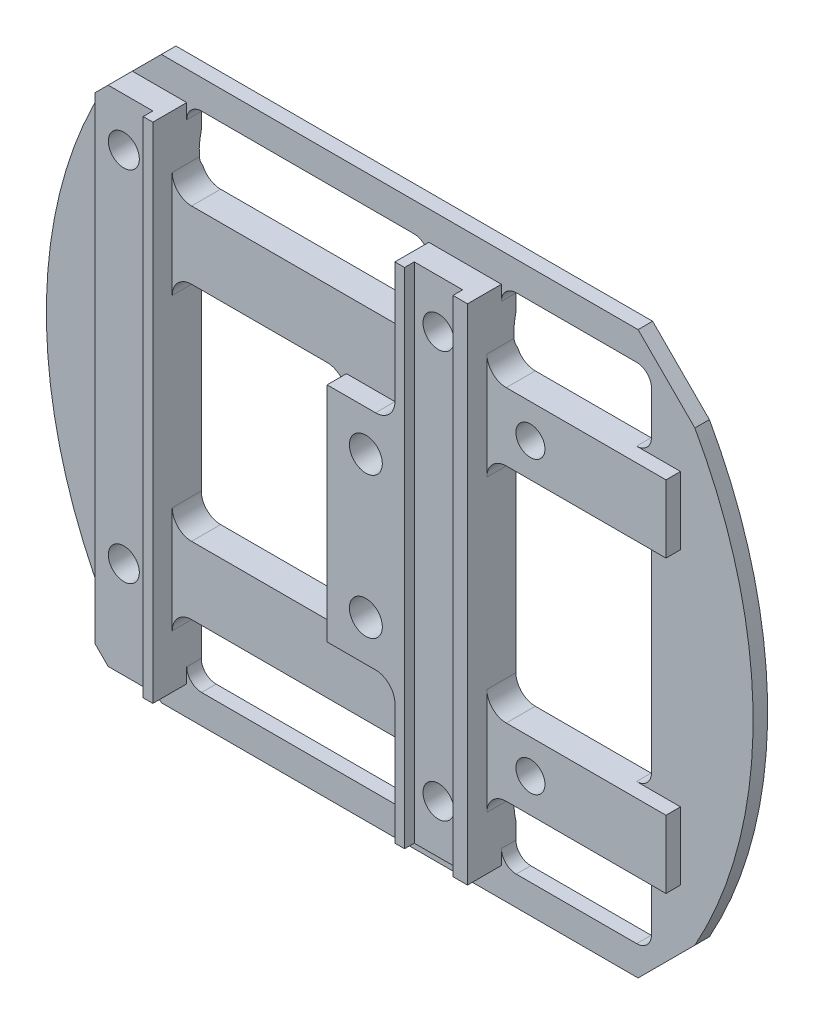
SolidWorks part; units mm, degrees
ref_plane "前视基准面" through (0, 0, 0) normal (0, 0, 1) x (1, 0, 0)
ref_plane "上视基准面" through (0, 0, 0) normal (0, 1, 0) x (1, 0, 0)
ref_plane "右视基准面" through (0, 0, 0) normal (1, 0, 0) x (0, 0, -1)
sketch "草图1" plane through (0, 0, 0) normal (0, 0, 1) x (1, 0, 0)
  line L0 (-31.173, 0) -> (39.916, 0) construction
  line L1 (-29, -29) -> (29, -29)
  line L2 (-29, -29) -> (-29, 29)
  line L3 (-29, 29) -> (29, 29)
  line L4 (29, -29) -> (29, 29)
  line L5 (-29, -29) -> (29, 29) construction
  line L6 (-29, 29) -> (29, -29) construction
  line L7 (12.0338, 26) -> (24.4662, 26)
  line L8 (10.5, 24.4662) -> (10.5, 20.0338)
  line L9 (12.0338, 18.5) -> (24.4662, 18.5)
  line L10 (26, 24.4662) -> (26, 20.0338)
  line L11 (10.5, 26) -> (26, 18.5) construction
  line L12 (10.5, 18.5) -> (26, 26) construction
  line L13 (12.0338, 11.5) -> (24.4662, 11.5)
  line L14 (10.5, 9.9662) -> (10.5, -9.9662)
  line L15 (12.0338, -11.5) -> (24.4662, -11.5)
  line L16 (26, 9.9662) -> (26, -9.9662)
  line L17 (10.5, 11.5) -> (26, -11.5) construction
  line L18 (10.5, -11.5) -> (26, 11.5) construction
  line L19 (12.0338, -18.5) -> (24.4662, -18.5)
  line L20 (10.5, -20.0338) -> (10.5, -24.4662)
  line L21 (12.0338, -26) -> (24.4662, -26)
  line L22 (26, -20.0338) -> (26, -24.4662)
  line L23 (10.5, -18.5) -> (26, -26) construction
  line L24 (10.5, -26) -> (26, -18.5) construction
  line L25 (-20.4662, 26) -> (1.4662, 26)
  line L26 (-22, 24.4662) -> (-22, 20.0338)
  line L27 (-20.4662, 18.5) -> (1.4662, 18.5)
  line L28 (3, 24.4662) -> (3, 20.0338)
  line L29 (-22, 26) -> (3, 18.5) construction
  line L30 (-22, 18.5) -> (3, 26) construction
  line L31 (-20.4662, 11.5) -> (-5.5338, 11.5)
  line L32 (-22, 9.9662) -> (-22, -9.9662)
  line L33 (-20.4662, -11.5) -> (-5.5338, -11.5)
  line L34 (-4, 9.9662) -> (-4, -9.9662)
  line L35 (-22, 11.5) -> (-4, -11.5) construction
  line L36 (-22, -11.5) -> (-4, 11.5) construction
  line L37 (-20.4662, -18.5) -> (1.4662, -18.5)
  line L38 (-22, -20.0338) -> (-22, -24.4662)
  line L39 (-20.4662, -26) -> (1.4662, -26)
  line L40 (3, -20.0338) -> (3, -24.4662)
  line L41 (-22, -18.5) -> (3, -26) construction
  line L42 (-22, -26) -> (3, -18.5) construction
  circle A0 centre (-26, 21) radius 1.6
  circle A1 centre (-26, -16) radius 1.6
  circle A2 centre (-15, 15) radius 1.5
  circle A3 centre (6.5, 21) radius 1.6
  circle A4 centre (15, 15) radius 1.5
  circle A5 centre (0, 7.3) radius 1.7
  circle A6 centre (15, -15) radius 1.5
  circle A7 centre (6.5, -21) radius 1.6
  circle A8 centre (-15, -15) radius 1.5
  circle A9 centre (0, -7.3) radius 1.7
  arc A10 (10.5, -20.0338) -> (12.0338, -18.5) centre (12.0338, -20.0338) cw
  arc A11 (24.4662, -18.5) -> (26, -20.0338) centre (24.4662, -20.0338) cw
  arc A12 (26, -24.4662) -> (24.4662, -26) centre (24.4662, -24.4662) cw
  arc A13 (12.0338, -26) -> (10.5, -24.4662) centre (12.0338, -24.4662) cw
  arc A14 (-20.4662, -26) -> (-22, -24.4662) centre (-20.4662, -24.4662) cw
  arc A15 (1.4662, -26) -> (3, -24.4662) centre (1.4662, -24.4662) ccw
  arc A16 (3, -20.0338) -> (1.4662, -18.5) centre (1.4662, -20.0338) ccw
  arc A17 (-20.4662, -18.5) -> (-22, -20.0338) centre (-20.4662, -20.0338) ccw
  arc A18 (-20.4662, 11.5) -> (-22, 9.9662) centre (-20.4662, 9.9662) ccw
  arc A19 (-20.4662, -11.5) -> (-22, -9.9662) centre (-20.4662, -9.9662) cw
  arc A20 (-5.5338, -11.5) -> (-4, -9.9662) centre (-5.5338, -9.9662) ccw
  arc A21 (-4, 9.9662) -> (-5.5338, 11.5) centre (-5.5338, 9.9662) ccw
  arc A22 (12.0338, 11.5) -> (10.5, 9.9662) centre (12.0338, 9.9662) ccw
  arc A23 (10.5, -9.9662) -> (12.0338, -11.5) centre (12.0338, -9.9662) ccw
  arc A24 (24.4662, -11.5) -> (26, -9.9662) centre (24.4662, -9.9662) ccw
  arc A25 (26, 9.9662) -> (24.4662, 11.5) centre (24.4662, 9.9662) ccw
  arc A26 (24.4662, 26) -> (26, 24.4662) centre (24.4662, 24.4662) cw
  arc A27 (26, 20.0338) -> (24.4662, 18.5) centre (24.4662, 20.0338) cw
  arc A28 (12.0338, 18.5) -> (10.5, 20.0338) centre (12.0338, 20.0338) cw
  arc A29 (10.5, 24.4662) -> (12.0338, 26) centre (12.0338, 24.4662) cw
  arc A30 (3, 24.4662) -> (1.4662, 26) centre (1.4662, 24.4662) ccw
  arc A31 (3, 20.0338) -> (1.4662, 18.5) centre (1.4662, 20.0338) cw
  arc A32 (-20.4662, 18.5) -> (-22, 20.0338) centre (-20.4662, 20.0338) cw
  arc A33 (-22, 24.4662) -> (-20.4662, 26) centre (-20.4662, 24.4662) cw
  point P0 (0, 0)
  point P6 (18.25, 22.25)
  point P11 (18.25, 0)
  point P16 (-9.5, 22.25)
  point P17 (18.25, -22.25)
  point P26 (-13, 0)
  point P31 (-9.5, -22.25)
  dimension "D21" = 3.2
  dimension "D22" = 3.2
  dimension "D27" = 3
  dimension "D28" = 3
  dimension "D29" = 3.2
  dimension "D30" = 3.4
  dimension "D43" = 1.5338
  dimension "D1" = 58
  dimension "D2" = 58
  dimension "D3" = 3
  dimension "D4" = 3
  dimension "D5" = 7.5
  dimension "D6" = 15.5
  dimension "D7" = 3
  dimension "D8" = 23
  dimension "D9" = 3
  dimension "D10" = 3
  dimension "D11" = 7.5
  dimension "D12" = 15.5
  dimension "D13" = 7
  dimension "D14" = 7
  dimension "D15" = 7
  dimension "D16" = 25
  dimension "D17" = 18
  dimension "D18" = 25
  dimension "D19" = 7.5
  dimension "D20" = 23
  dimension "D23" = 3
  dimension "D24" = 3
  dimension "D25" = 37
  dimension "D26" = 13
  dimension "D31" = 21
  dimension "D32" = 7.3
  dimension "D33" = 15
  dimension "D34" = 15
  dimension "D35" = 14
  dimension "D36" = 30
  dimension "D37" = 32.5
  dimension "D38" = 29
  dimension "D39" = 15.5
  dimension "D40" = 7.5
  dimension "D41" = 3
  dimension "D42" = 3
extrude "凸台-拉伸1" add sketch "草图1" along normal blind 5
sketch "草图2" plane through (0, 0, 5) normal (0, 0, 1) x (1, 0, 0)
  line L0 (-29, -26) -> (-29, -29)
  line L2 (10.5, 18.5) -> (10.5, 26)
  line L3 (10.5, 26) -> (3, 26)
  line L4 (3, 26) -> (3, 11.5)
  line L5 (3, 11.5) -> (-4, 11.5)
  line L6 (-4, 11.5) -> (-4, -8.613)
  line L7 (-4, -9.9662) -> (-4, 9.9662) construction
  line L8 (-4, -8.613) -> (-4, -11.5)
  line L9 (-4, -11.5) -> (3, -11.5)
  line L10 (3, -11.5) -> (3, -26)
  line L11 (3, -26) -> (10.5, -26)
  line L12 (10.5, -26) -> (10.5, -18.5)
  line L13 (-29, 29) -> (29, 29)
  line L14 (-29, 26) -> (-22, 26)
  line L15 (-29, 29) -> (-29, -29) construction
  line L16 (-22, 26) -> (-22, -26)
  line L17 (-22, -26) -> (-29, -26)
  line L18 (10.5, 18.5) -> (10.5, -18.5)
  line L19 (-29, 29) -> (-29, 26)
  line L20 (-29, -29) -> (29, -29)
  line L21 (29, 29) -> (29, -29)
  line L22 (-29, 29) -> (29, -29) construction
  line L23 (-29, -29) -> (29, 29) construction
  point P0 (0, 0)
extrude "切除-拉伸1" cut sketch "草图2" against normal blind 3.5
sketch "草图3" plane through (0, 0, 1.5) normal (0, 0, 1) x (1, 0, 0)
  line L0 (12.0338, 18.5) -> (10.5, 18.5)
  line L1 (10.5, 26) -> (10.5, -26) construction
  line L2 (10.5, 18.5) -> (10.5, 11.5)
  line L3 (10.5, 11.5) -> (29, 11.5)
  line L4 (29, -29) -> (29, 29) construction
  line L5 (29, 11.5) -> (29, 18.5)
  line L6 (29, 18.5) -> (10.5, 18.5)
  line L7 (12.0338, -11.5) -> (10.5, -11.5)
  line L8 (10.5, -11.5) -> (10.5, -18.5)
  line L9 (10.5, -18.5) -> (29, -18.5)
  line L10 (29, -18.5) -> (29, -11.5)
  line L11 (29, -11.5) -> (10.5, -11.5)
  line L12 (1.4662, 18.5) -> (3, 18.5)
  line L13 (3, 20.0338) -> (3, 11.5) construction
  line L14 (3, 18.5) -> (3, 11.5)
  line L15 (3, 11.5) -> (-22, 11.5)
  line L16 (-22, 26) -> (-22, -26) construction
  line L17 (-22, 11.5) -> (-22, 18.5)
  line L18 (-22, 20.0338) -> (-22, 9.9662) construction
  line L19 (-22, 18.5) -> (1.4662, 18.5)
  line L20 (3, -11.5) -> (-22, -11.5)
  line L21 (-22, -11.5) -> (-22, -18.5)
  line L22 (-22, -18.5) -> (3, -18.5)
  line L23 (3, -11.5) -> (3, -20.0338) construction
  line L24 (3, -18.5) -> (3, -11.5)
  circle M1 centre (15, 15) radius 1.5
  circle M2 centre (15, -15) radius 1.5
  line M3 (12.0338, -18.5) -> (24.4662, -18.5)
  line M19 (29, -29) -> (29, 29)
  line M35 (24.4662, 18.5) -> (12.0338, 18.5)
  line M37 (10.5, 20.0338) -> (10.5, 9.9662)
  line M39 (12.0338, 11.5) -> (24.4662, 11.5)
  line M43 (24.4662, -11.5) -> (12.0338, -11.5)
  line M45 (10.5, -9.9662) -> (10.5, -20.0338)
extrude "凸台-拉伸2" add sketch "草图3" along normal blind 1.5 contours L22 L24 L20 L21 | L19 L17 L15 L14 L12 | L6 L0 L3 M19 M35 M37 M39 M1 | L11 L7 L9 M19 M43 M45 M3 M2 region at (20.0242, 15, 1.5) region at (20.0242, -15, 1.5) region at (-9.5, 15, 1.5) region at (-9.5, -15, 1.5)
fillet "圆角2" radius 2 1 edges at (-22, -11.5, 2.25)
fillet "圆角3" radius 2 11 edges at (10.5, 11.5, 2.25) (-22, 11.5, 2.25) (-4, 11.5, 2.25) (-22, -18.5, 2.25) (3, -18.5, 2.25) (10.5, -18.5, 2.25) (10.5, -11.5, 2.25) (10.5, 18.5, 2.25) (-22, 18.5, 2.25) (3, 18.5, 2.25) (-4, -11.5, 2.25)
sketch "草图4" plane through (0, -26, 0) normal (0, -1, 0) x (1, 0, 0)
  line L0 (-25.5, 5) -> (-25.5, -4.7601) construction
  line L1 (-22, 5) -> (-29, 5) construction
  line L2 (-22, 1.5) -> (-22, 5) construction
  line L3 (-28, 4) -> (-23, 4)
  line L5 (-28, 5) -> (-23, 5)
  line L6 (-23, 4) -> (-23, 5)
  line L7 (-28, 4) -> (-23, 5) construction
  line L8 (-28, 5) -> (-23, 4) construction
  line L9 (6.5, 5.6001) -> (6.5, -1.0614) construction
  line L10 (3, 5) -> (10.5, 5) construction
  line L11 (4, 4) -> (9, 4)
  line L12 (4, 4) -> (4, 5)
  line L13 (4, 5) -> (9, 5)
  line L14 (9, 4) -> (9, 5)
  line L15 (4, 4) -> (9, 5) construction
  line L16 (4, 5) -> (9, 4) construction
  line L18 (3, 1.5) -> (3, 5) construction
  line L20 (-28, 5) -> (-29, 5)
  line L22 (-28, 4) -> (-29, 4)
  line L23 (-29, 5) -> (-29, 4)
  point P4 (-25.5, 4.5)
  point P13 (6.5, 4.5)
  dimension "D1" = 1
  dimension "D2" = 1
  dimension "D3" = 1
  dimension "D4" = 1
  dimension "D5" = 5
extrude "切除-拉伸2" cut sketch "草图4" against normal up to surface (52 mm away) up to face at (-25.5, 26, 3.25)
ref_plane "基准面1" through (-26, 0, 0) normal (-1, 0, 0) x (0, 0, 1)
sketch "草图12" plane through (0, 0, 0) normal (0, 0, -1) x (-1, 0, 0)
  line L0 (-11, 29) -> (-11, -29) construction
  line L1 (-29, 29) -> (29, 29) construction
  line L2 (29, -29) -> (-29, -29) construction
  line L3 (29, 29) -> (29, -29) construction
  line L4 (29, 25.6174) -> (29, -25.6174)
  line L5 (0, 29) -> (0, -29) construction
  line L6 (-29, 25.6174) -> (-29, -25.6174)
  arc A0 (29, -25.6174) -> (29, 25.6174) centre (-11, 0) ccw
  arc A1 (-29, -25.6174) -> (-29, 25.6174) centre (11, 0) cw
  dimension "D2" = 95
  dimension "D1" = 40
extrude "凸台-拉伸6" add sketch "草图12" against normal blind 1.5
sketch "草图5" plane through (-26, 0, 0) normal (-1, 0, 0) x (0, 0, 1)
  line L0 (0, 21) -> (5.3114, 21) construction
  line L2 (0, 24.4662) -> (0, 20.5) construction
  line L3 (0, 22.6) -> (0, 19.4) construction
  line L4 (1.6, 21) -> (1.6, 22.6)
  line L6 (1.6, 22.6) -> (0, 25.3713)
  line L7 (1.6, 21) -> (0, 21)
  line L11 (0, 25.3713) -> (0, 21)
  dimension "D1" = 1.6
  dimension "D2" = 1.6
  dimension "D3" = 60
revolve "切除-旋转1" cut sketch "草图5" angle 360 about L0
pattern_linear "阵列(线性)1" count 2 spacing 37 along (0, -1, 0) of "切除-旋转1"
pattern_linear "阵列(线性)2" count 2 spacing 32.5 along (1, 0, 0) of "切除-旋转1"
ref_plane "基准面2" through (6.5, 0, 0) normal (1, 0, 0) x (0, 0, -1)
sketch "草图6" plane through (6.5, 0, 0) normal (1, 0, 0) x (0, 0, -1)
  line L0 (0, -21) -> (-1.6, -21)
  line L1 (0, -22.6) -> (0, -19.4) construction
  line L2 (-1.6, -21) -> (-1.6, -22.6)
  line L3 (-1.6, -22.6) -> (0, -25.3713)
  line L4 (0, -26) -> (0, -24.4662) construction
  line L5 (0, -25.3713) -> (0, -21)
  dimension "D1" = 1.6
  dimension "D2" = 1.6
  dimension "D3" = 60
revolve "切除-旋转2" cut sketch "草图6" angle 360 about L0
fillet "圆角4" radius 2 2 edges at (3, -11.5, 4) (3, 11.5, 4)
sketch "草图7" plane through (0, 0, 0) normal (0, 0, -1) x (-1, 0, 0)
  line L0 (-29, 25.6174) -> (-29, -25.6174)
  line L1 (29, 25.6174) -> (29, -25.6174)
  arc A0 (29, -25.6174) -> (29, 25.6174) centre (-11, 0) ccw
  arc A1 (-29, 25.6174) -> (-29, -25.6174) centre (11, 0) ccw
  dimension "D2" = 95
  dimension "D4" = 95
extrude "凸台-拉伸4" [suppressed] add sketch "草图7" against normal blind 1.5 separate body
sketch "草图8" [suppressed] plane through (0, 0, 0) normal (0, 0, -1) x (-1, 0, 0)
  arc A0 (0, 46.2088) -> (0, -46.2088) centre (11, 0) ccw
  arc A1 (0, -46.2088) -> (0, 46.2088) centre (-11, 0) ccw
  circle A2 centre (0, 0) radius 46.2088
extrude "切除-拉伸3" [suppressed] cut sketch "草图8" against normal blind 5 contours A0 A2 | A1 A2
sketch "草图11" plane through (29, 0, 0) normal (1, 0, 0) x (0, 0, -1)
  line L0 (-3, 11.5) -> (0, 11.5) construction
  line L1 (-3, 18.5) -> (-1.5, 18.5)
  line L2 (-3, 18.5) -> (-3, 11.5)
  line L3 (-3, 11.5) -> (-1.5, 11.5)
  line L4 (-1.5, 18.5) -> (-1.5, 11.5)
  line L5 (-3, -18.5) -> (0, -18.5) construction
  line L6 (-3, -11.5) -> (-1.5, -11.5)
  line L7 (-3, -11.5) -> (-3, -18.5)
  line L8 (-3, -18.5) -> (-1.5, -18.5)
  line L9 (-1.5, -11.5) -> (-1.5, -18.5)
extrude "凸台-拉伸5" [suppressed] add sketch "草图11" along normal up to surface (3.7493 mm away)
sketch "草图13" plane through (0, 0, 0) normal (0, 0, -1) x (-1, 0, 0)
  arc A0 (0, -46.2088) -> (0, 46.2088) centre (-11, 0) ccw
  arc A1 (0, 46.2088) -> (0, -46.2088) centre (11, 0) ccw
  circle A2 centre (0, 0) radius 50.4559
extrude "切除-拉伸4" cut sketch "草图13" against normal blind 7
chamfer "倒角1" distance 2 angle 45 1 edges at (-26.6198, 29, 0.75) first distance on face at (0, 29, 0.75)
chamfer "倒角2" distance 2 angle 45 3 edges at (-26.6198, -29, 0.75) (26.6198, -29, 0.75) (26.6198, 29, 0.75) first distance on face at (0, -29, 0.75) first distance on face at (1, 29, 0.75)
